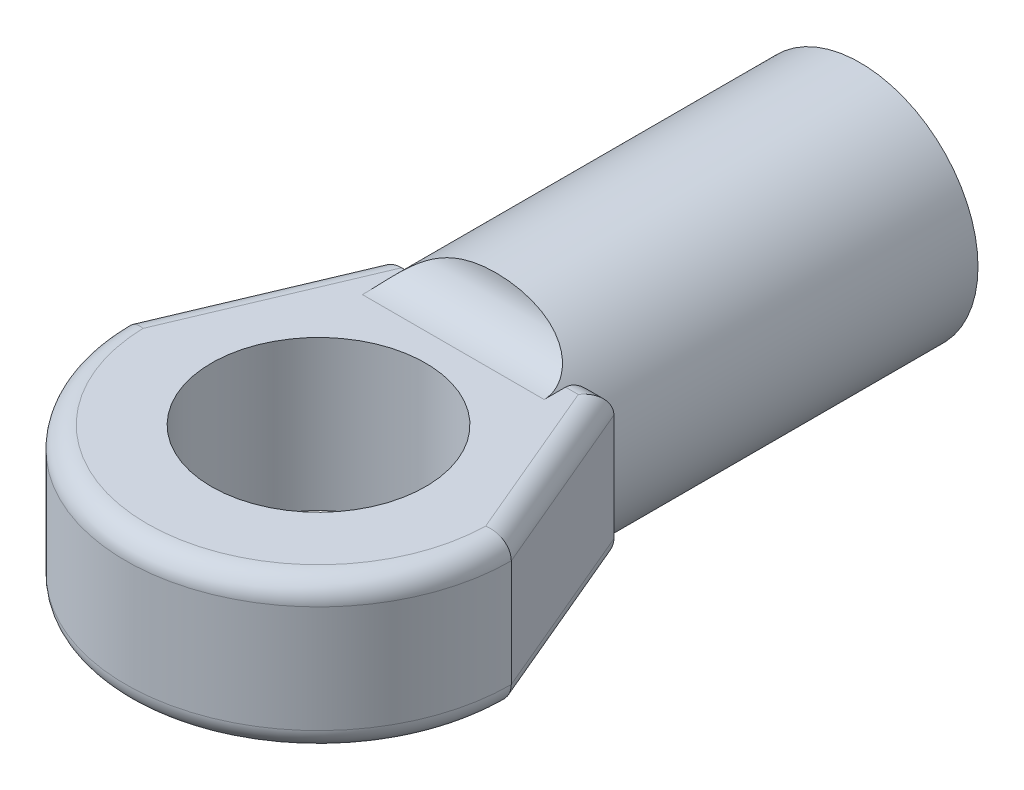
SolidWorks part; units mm, degrees
material "5052-O"
ref_plane "正面" through (0, 0, 0) normal (0, 0, 1) x (1, 0, 0)
ref_plane "平面" through (0, 0, 0) normal (0, 1, 0) x (1, 0, 0)
ref_plane "右側面" through (0, 0, 0) normal (1, 0, 0) x (0, 0, -1)
sketch "ｽｹｯﾁ1" plane through (0, 0, 0) normal (0, 1, 0) x (1, 0, 0)
  line L0 (0, 0) -> (4.5, 0)
  line L1 (4.5, 0) -> (-4.5, 0)
  line L2 (0, 0) -> (0, 4.1458)
  line L3 (0, 4.1458) -> (-2.75, 4.1458)
  line L4 (-2.75, 4.1458) -> (-4.5, 0)
  line L5 (0, 4.1458) -> (2.75, 4.1458)
  line L6 (2.75, 4.1458) -> (4.5, 0)
  arc A0 (-4.5, 0) -> (4.5, 0) centre (0, 0) ccw
extrude "ﾎﾞｽ - 押し出し1" add sketch "ｽｹｯﾁ1" along normal blind 3.5 contours L3 L4 L1 L2 | L1 A0 L0 | L6 L5 L2 L0 region at (1.8477, 0, -1.9061) region at (0, 0, 1.9099) region at (-1.8477, 0, -1.9061)
sketch "ｽｹｯﾁ2" plane through (0, 0, -4.1458) normal (0, 0, -1) x (-1, 0, 0)
  circle A0 centre (0, 1.75) radius 2.75
extrude "ﾎﾞｽ - 押し出し2" add sketch "ｽｹｯﾁ2" along normal blind 8.5
fillet "ﾌｨﾚｯﾄ1" radius 1 1 edges at (0, 0, -4.1458)
fillet "ﾌｨﾚｯﾄ2" radius 1 1 edges at (0, 3.5, -4.1458)
sketch "ｽｹｯﾁ3" plane through (0, 3.5, 0) normal (0, 1, 0) x (1, 0, 0)
  circle A0 centre (0, 0) radius 2.5
extrude "ｶｯﾄ - 押し出し1" cut sketch "ｽｹｯﾁ3" against normal through all
fillet "ﾌｨﾚｯﾄ3" radius 0.5 9 edges at (-2.4357, 0, -4.1458) (-3.625, 0, -2.0729) (0, 0, 4.5) (3.625, 0, -2.0729) (2.4357, 0, -4.1458) (2.4357, 3.5, -4.1458) (-3.625, 3.5, -2.0729) (0, 3.5, 4.5) (3.625, 3.5, -2.0729)
